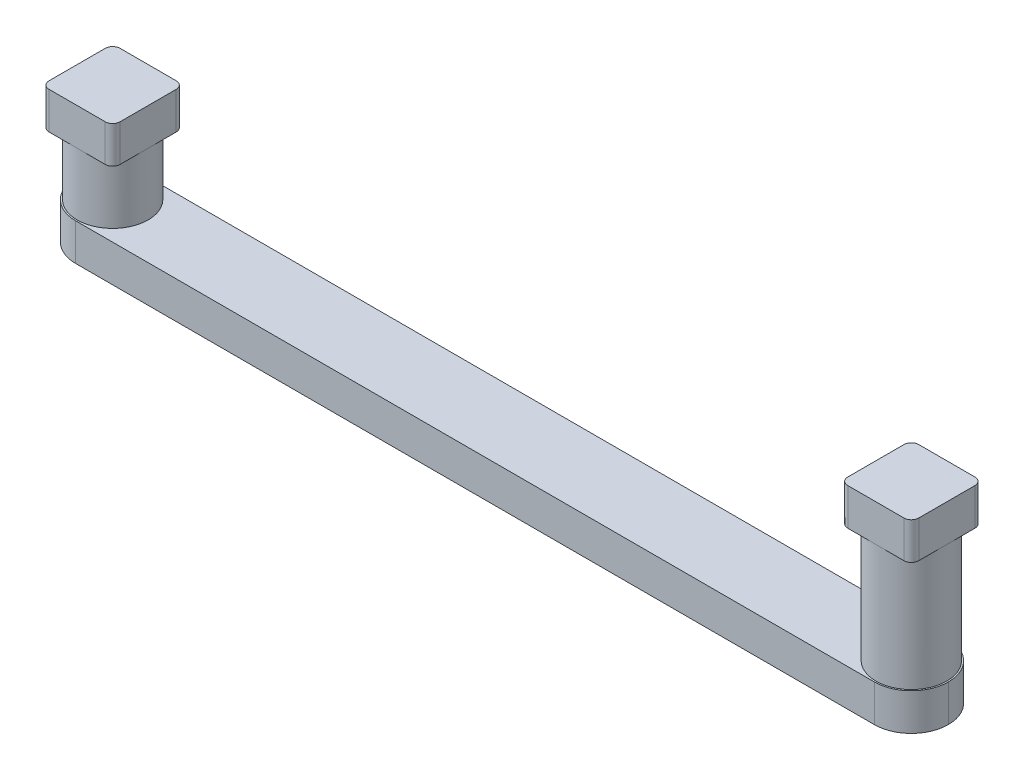
SolidWorks part; units mm, degrees
ref_plane "Front Plane" through (0, 0, 0) normal (0, 0, 1) x (1, 0, 0)
ref_plane "Top Plane" through (0, 0, 0) normal (0, 1, 0) x (1, 0, 0)
ref_plane "Right Plane" through (0, 0, 0) normal (1, 0, 0) x (0, 0, -1)
sketch "Sketch1" plane through (0, 0, 0) normal (0, 1, 0) x (1, 0, 0)
  line L1 (37.465, -3.175) -> (-37.465, -3.175)
  line L2 (37.465, -3.175) -> (37.465, 3.175)
  line L3 (37.465, 3.175) -> (-37.465, 3.175)
  line L4 (-37.465, -3.175) -> (-37.465, 3.175)
  line L5 (37.465, -3.175) -> (-37.465, 3.175) construction
  line L6 (37.465, 3.175) -> (-37.465, -3.175) construction
  point P0 (0, 0)
  dimension "D1" = 6.35
  dimension "D2" = 74.93
extrude "Boss-Extrude1" add sketch "Sketch1" along normal blind 3.175
sketch "Sketch2" plane through (0, 3.175, 0) normal (0, 1, 0) x (1, 0, 0)
  line L0 (0, 3.175) -> (0, -3.175) construction
  line L1 (37.465, 3.175) -> (-37.465, 3.175) construction
  line L2 (-37.465, -3.175) -> (37.465, -3.175) construction
  line L3 (0, 0) -> (-34.29, 0) construction
  circle A0 centre (-34.29, 0) radius 3.048
  dimension "D1" = 6.096
  dimension "D2" = 34.29
extrude "Boss-Extrude2" add sketch "Sketch2" along normal blind 5.334
sketch "Sketch3" plane through (0, 8.509, 0) normal (0, 1, 0) x (1, 0, 0)
  line L0 (-34.29, 0) -> (-34.29, 3.048) construction
  line L1 (-34.29, 3.048) -> (-37.338, 3.048) construction
  line L2 (-37.338, 3.048) -> (-37.338, 0) construction
  line L3 (-37.338, 0) -> (-34.29, 0) construction
  line L5 (-31.242, -3.048) -> (-37.338, -3.048)
  line L6 (-31.242, -3.048) -> (-31.242, 3.048)
  line L7 (-31.242, 3.048) -> (-37.338, 3.048)
  line L8 (-37.338, -3.048) -> (-37.338, 3.048)
  line L9 (-31.242, -3.048) -> (-37.338, 3.048) construction
  line L10 (-31.242, 3.048) -> (-37.338, -3.048) construction
  circle A0 centre (-34.29, 0) radius 3.048 construction
extrude "Boss-Extrude3" add sketch "Sketch3" along normal blind 3.175
sketch "Sketch4" plane through (0, 3.175, 0) normal (0, 1, 0) x (1, 0, 0)
  line L0 (0, 0) -> (34.29, 0) construction
  circle A0 centre (34.29, 0) radius 3.048
  dimension "D2" = 6.096
  dimension "D1" = 34.29
extrude "Boss-Extrude4" add sketch "Sketch4" along normal blind 10.16 contours A0
sketch "Sketch5" plane through (0, 13.335, 0) normal (0, 1, 0) x (1, 0, 0)
  line L0 (34.29, 0) -> (34.29, 3.048) construction
  line L1 (34.29, 3.048) -> (37.338, 3.048) construction
  line L2 (37.338, 3.048) -> (37.338, 0) construction
  line L4 (31.242, -3.048) -> (37.338, -3.048)
  line L5 (31.242, -3.048) -> (31.242, 3.048)
  line L6 (31.242, 3.048) -> (37.338, 3.048)
  line L7 (37.338, -3.048) -> (37.338, 3.048)
  line L8 (31.242, -3.048) -> (37.338, 3.048) construction
  line L9 (31.242, 3.048) -> (37.338, -3.048) construction
  circle A0 centre (34.29, 0) radius 3.048 construction
  circle A1 centre (34.29, 0) radius 3.048 construction
extrude "Boss-Extrude5" add sketch "Sketch5" along normal blind 3.175
fillet "Fillet1" radius 0.635 8 edges at (-37.338, 10.0965, 3.048) (-31.242, 10.0965, 3.048) (-37.338, 10.0965, -3.048) (-31.242, 10.0965, -3.048) (31.242, 14.9225, -3.048) (31.242, 14.9225, 3.048) (37.338, 14.9225, -3.048) (37.338, 14.9225, 3.048)
fillet "Fillet2" radius 3.175 4 edges at (-37.465, 1.5875, 3.175) (-37.465, 1.5875, -3.175) (37.465, 1.5875, -3.175) (37.465, 1.5875, 3.175)
